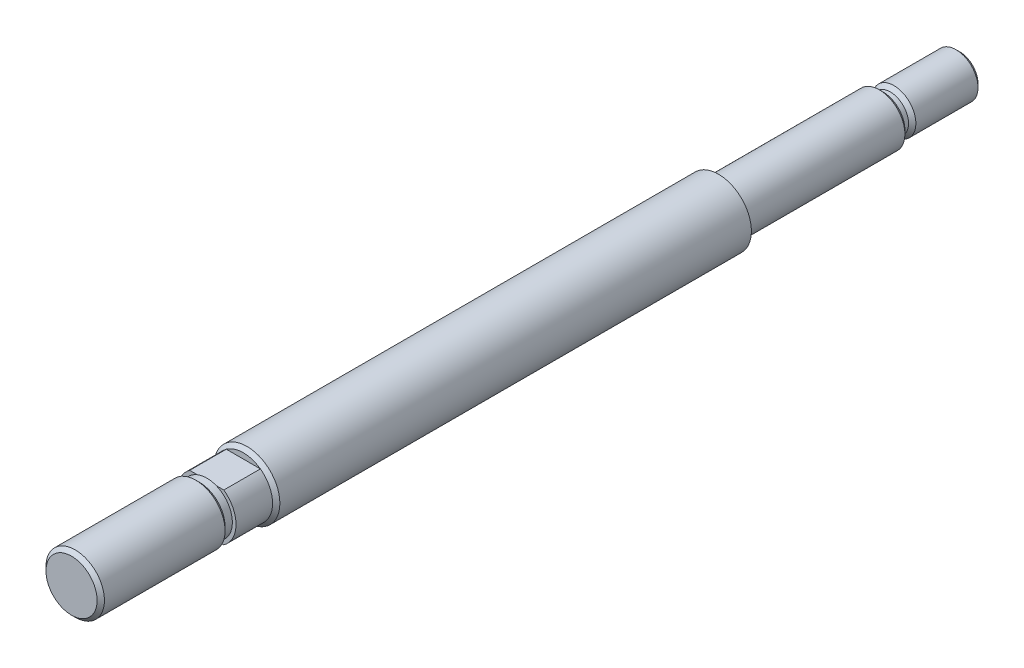
SolidWorks part; units mm, degrees
ref_plane "Front Plane" through (0, 0, 0) normal (0, 0, 1) x (1, 0, 0)
ref_plane "Top Plane" through (0, 0, 0) normal (0, 1, 0) x (1, 0, 0)
ref_plane "Right Plane" through (0, 0, 0) normal (1, 0, 0) x (0, 0, -1)
sketch "Sketch1" plane through (0, 0, 0) normal (0, 0, 1) x (1, 0, 0)
  circle A0 centre (0, 0) radius 9
  dimension "D1" = 18
extrude "Boss-Extrude1" add sketch "Sketch1" along normal mid plane 243
sketch "Sketch2" plane through (0, 0, -121.5) normal (0, 0, -1) x (-1, 0, 0)
  circle A0 centre (0, 0) radius 6
  dimension "D1" = 12
extrude "Cut-Extrude2" cut sketch "Sketch2" against normal blind 19 flip side to cut
cosmetic thread "Cosmetic Thread1" parameters "D2"=10.072
sketch "Sketch3" plane through (0, 0, -102.5) normal (0, 0, -1) x (-1, 0, 0)
  circle A0 centre (0, 0) radius 5
  dimension "D1" = 10
extrude "Cut-Extrude3" cut sketch "Sketch3" against normal blind 2 flip side to cut
sketch "Sketch4" plane through (0, 0, -100.5) normal (0, 0, -1) x (-1, 0, 0)
  circle A0 centre (0, 0) radius 7
  dimension "D1" = 14
extrude "Cut-Extrude4" cut sketch "Sketch4" against normal blind 45 flip side to cut
chamfer "Chamfer1" distance 1 angle 45 3 edges at (-7, 0, -100.5) (-6, 0, -102.5) (-6, 0, -121.5)
sketch "Sketch5" plane through (0, 0, 121.5) normal (0, 0, 1) x (1, 0, 0)
  circle A0 centre (0, 0) radius 6.5
  dimension "D1" = 13
extrude "Cut-Extrude5" cut sketch "Sketch5" against normal blind 47 flip side to cut
sketch "Sketch6" plane through (0, 0, 74.5) normal (0, 0, 1) x (1, 0, 0)
  circle A0 centre (0, 0) radius 8
  dimension "D1" = 16
extrude "Boss-Extrude2" add sketch "Sketch6" along normal blind 10
sketch "Sketch8" plane through (0, 0, 121.5) normal (0, 0, 1) x (1, 0, 0)
  circle A0 centre (0, 0) radius 8
  dimension "D1" = 16
extrude "Boss-Extrude3" add sketch "Sketch8" against normal blind 35
cosmetic thread "Cosmetic Thread3" parameters "D2"=13.797
chamfer "Chamfer3" distance 1 angle 45 3 edges at (9, 0, 74.5) (8, 0, 86.5) (8, 0, 121.5)
sketch "Sketch12" plane through (0, 0, 86.5) normal (0, 0, -1) x (-1, 0, 0)
  circle A0 centre (0, 0) radius 7
extrude "Boss-Extrude4" add sketch "Sketch12" along normal up to next
sketch "Sketch14" plane through (0, 0, 0) normal (1, 0, 0) x (0, 0, -1)
  line L0 (-74.5, 0) -> (-84.5, 0) construction
  line L1 (-74.5, 8) -> (-74.5, -8) construction
  line L2 (-84.5, 7) -> (-84.5, -7) construction
  line L3 (-84.5, 6.5) -> (-84.5, 8)
  line L4 (-84.5, 8) -> (-84.5, -8) construction
  line L5 (-84.5, 6.5) -> (-74.5, 6.5)
  line L6 (-84.5, 8) -> (-74.5, 8)
  line L7 (-84.5, -6.5) -> (-74.5, -6.5)
  line L8 (-74.5, 8) -> (-74.5, 6.5)
  line L9 (-84.5, -6.5) -> (-84.5, -8)
  line L10 (-84.5, -8) -> (-74.5, -8)
  line L11 (-74.5, -8) -> (-74.5, -6.5)
  dimension "D1" = 6.5
extrude "Cut-Extrude7" cut sketch "Sketch14" against normal mid plane 35
